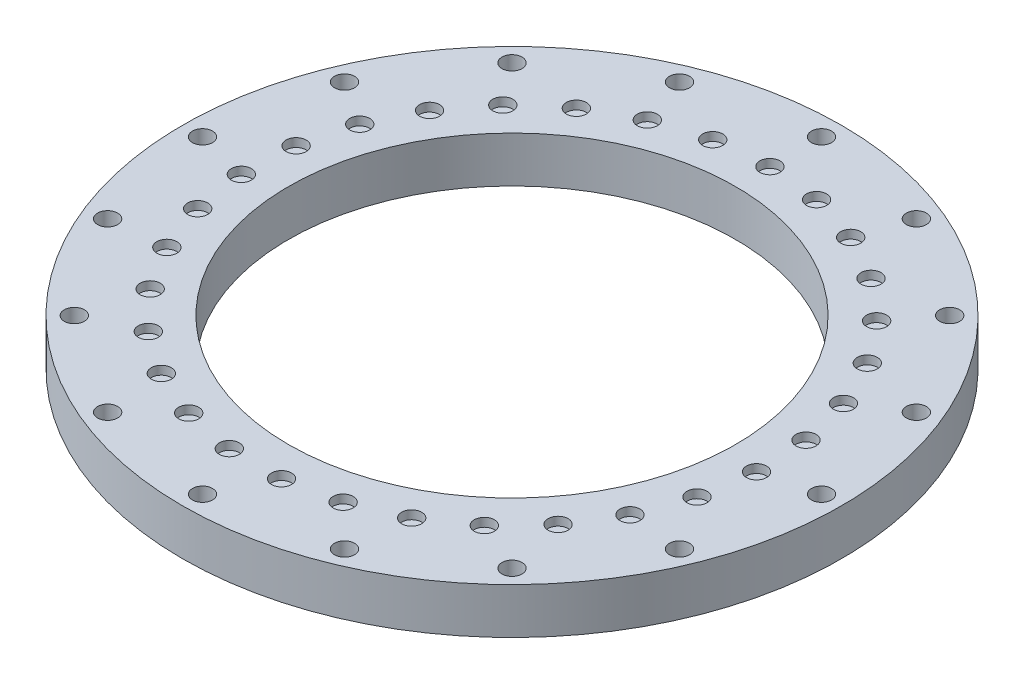
SolidWorks part; units mm, degrees
ref_plane "Front Plane" through (0, 0, 0) normal (0, 0, 1) x (1, 0, 0)
ref_plane "Top Plane" through (0, 0, 0) normal (0, 1, 0) x (1, 0, 0)
ref_plane "Right Plane" through (0, 0, 0) normal (1, 0, 0) x (0, 0, -1)
sketch "Sketch1" plane through (0, 0, 0) normal (0, 1, 0) x (1, 0, 0)
  circle A0 centre (0, 0) radius 57.5
  circle A1 centre (0, 0) radius 39
  dimension "D1" = 115
  dimension "D2" = 78
extrude "Boss-Extrude1" add sketch "Sketch1" along normal blind 8
sketch "Sketch2" plane through (0, 8, 0) normal (0, 1, 0) x (1, 0, 0)
  circle A0 centre (0, 0) radius 54 construction
  circle A1 centre (0, 54) radius 1.75
  circle A2 centre (20.6649, 49.8895) radius 1.75
  circle A3 centre (38.1838, 38.1838) radius 1.75
  circle A4 centre (49.8895, 20.6649) radius 1.75
  circle A5 centre (54, 0) radius 1.75
  circle A6 centre (49.8895, -20.6649) radius 1.75
  circle A7 centre (38.1838, -38.1838) radius 1.75
  circle A8 centre (20.6649, -49.8895) radius 1.75
  circle A9 centre (0, -54) radius 1.75
  circle A10 centre (-20.6649, -49.8895) radius 1.75
  circle A11 centre (-38.1838, -38.1838) radius 1.75
  circle A12 centre (-49.8895, -20.6649) radius 1.75
  circle A13 centre (-54, 0) radius 1.75
  circle A14 centre (-49.8895, 20.6649) radius 1.75
  circle A15 centre (-38.1838, 38.1838) radius 1.75
  circle A16 centre (-20.6649, 49.8895) radius 1.75
  point P37 (0, 0)
  dimension "D1" = 108
  dimension "D2" = 3.5
  dimension "D3" = 16
extrude "Cut-Extrude1" cut sketch "Sketch2" against normal blind 17
sketch "Sketch3" plane through (0, 8, 0) normal (0, 1, 0) x (1, 0, 0)
  circle A0 centre (0, 0) radius 45 construction
  circle A1 centre (0, 45) radius 1.75
  circle A2 centre (9.0584, 44.0788) radius 1.75
  circle A3 centre (17.746, 41.3531) radius 1.75
  circle A4 centre (25.7071, 36.9344) radius 1.75
  circle A5 centre (32.6157, 31.0035) radius 1.75
  circle A6 centre (38.189, 23.8034) radius 1.75
  circle A7 centre (42.1988, 15.6287) radius 1.75
  circle A8 centre (44.4811, 6.8142) radius 1.75
  circle A9 centre (44.9422, -2.2792) radius 1.75
  circle A10 centre (43.5635, -11.2794) radius 1.75
  circle A11 centre (40.4012, -19.8177) radius 1.75
  circle A12 centre (35.5849, -27.5448) radius 1.75
  circle A13 centre (29.3118, -34.1441) radius 1.75
  circle A14 centre (21.8386, -39.3456) radius 1.75
  circle A15 centre (13.4713, -42.9363) radius 1.75
  circle A16 centre (4.5526, -44.7691) radius 1.75
  circle A17 centre (-4.5526, -44.7691) radius 1.75
  circle A18 centre (-13.4713, -42.9363) radius 1.75
  circle A19 centre (-21.8386, -39.3456) radius 1.75
  circle A20 centre (-29.3118, -34.1441) radius 1.75
  circle A21 centre (-35.5849, -27.5448) radius 1.75
  circle A22 centre (-40.4012, -19.8177) radius 1.75
  circle A23 centre (-43.5635, -11.2794) radius 1.75
  circle A24 centre (-44.9422, -2.2792) radius 1.75
  circle A25 centre (-44.4811, 6.8142) radius 1.75
  circle A26 centre (-42.1988, 15.6287) radius 1.75
  circle A27 centre (-38.189, 23.8034) radius 1.75
  circle A28 centre (-32.6157, 31.0035) radius 1.75
  circle A29 centre (-25.7071, 36.9344) radius 1.75
  circle A30 centre (-17.746, 41.3531) radius 1.75
  circle A31 centre (-9.0584, 44.0788) radius 1.75
  point P67 (0, 0)
  dimension "D1" = 90
  dimension "D2" = 3.5
  dimension "D3" = 31
extrude "Cut-Extrude2" cut sketch "Sketch3" against normal blind 1.5
sketch "Sketch4" plane through (0, 0, 0) normal (0, -1, 0) x (1, 0, 0)
  circle A0 centre (0, 0) radius 50
  dimension "D1" = 100
